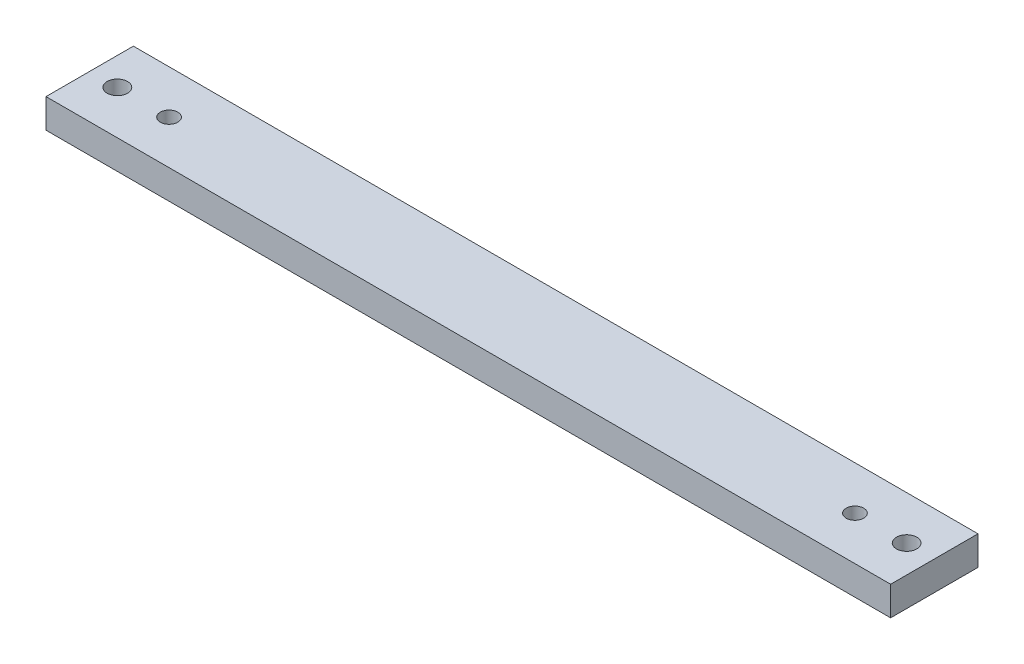
SolidWorks part; units mm, degrees
ref_plane "Front Plane" through (0, 0, 0) normal (0, 0, 1) x (1, 0, 0)
ref_plane "Top Plane" through (0, 0, 0) normal (0, 1, 0) x (1, 0, 0)
ref_plane "Right Plane" through (0, 0, 0) normal (1, 0, 0) x (0, 0, -1)
sketch "Sketch3" plane through (0, 0, 0) normal (0, 1, 0) x (1, 0, 0)
  line L1 (0, 80) -> (580, 80)
  line L2 (0, 80) -> (0, 20)
  line L3 (0, 20) -> (580, 20)
  line L4 (580, 80) -> (580, 20)
  dimension "D1" = 580
  dimension "D2" = 60
extrude "Boss-Extrude1" add sketch "Sketch3" along normal blind 20
sketch "Sketch4" plane through (0, 20, 0) normal (0, 1, 0) x (1, 0, 0)
  circle A0 centre (19, 50) radius 7
  circle A1 centre (54.5, 50) radius 6
  circle A2 centre (525.5, 50) radius 6
  circle A3 centre (561, 50) radius 7
  point P2 (0, 0)
  point P3 (0, 0)
  point P10 (0, 0)
  dimension "D1" = 12
  dimension "D3" = 14
  dimension "D4" = 12
  dimension "D5" = 14
  dimension "D2" = 35.5
  dimension "D6" = 35.5
extrude "Cut-Extrude1" cut sketch "Sketch4" against normal through all
